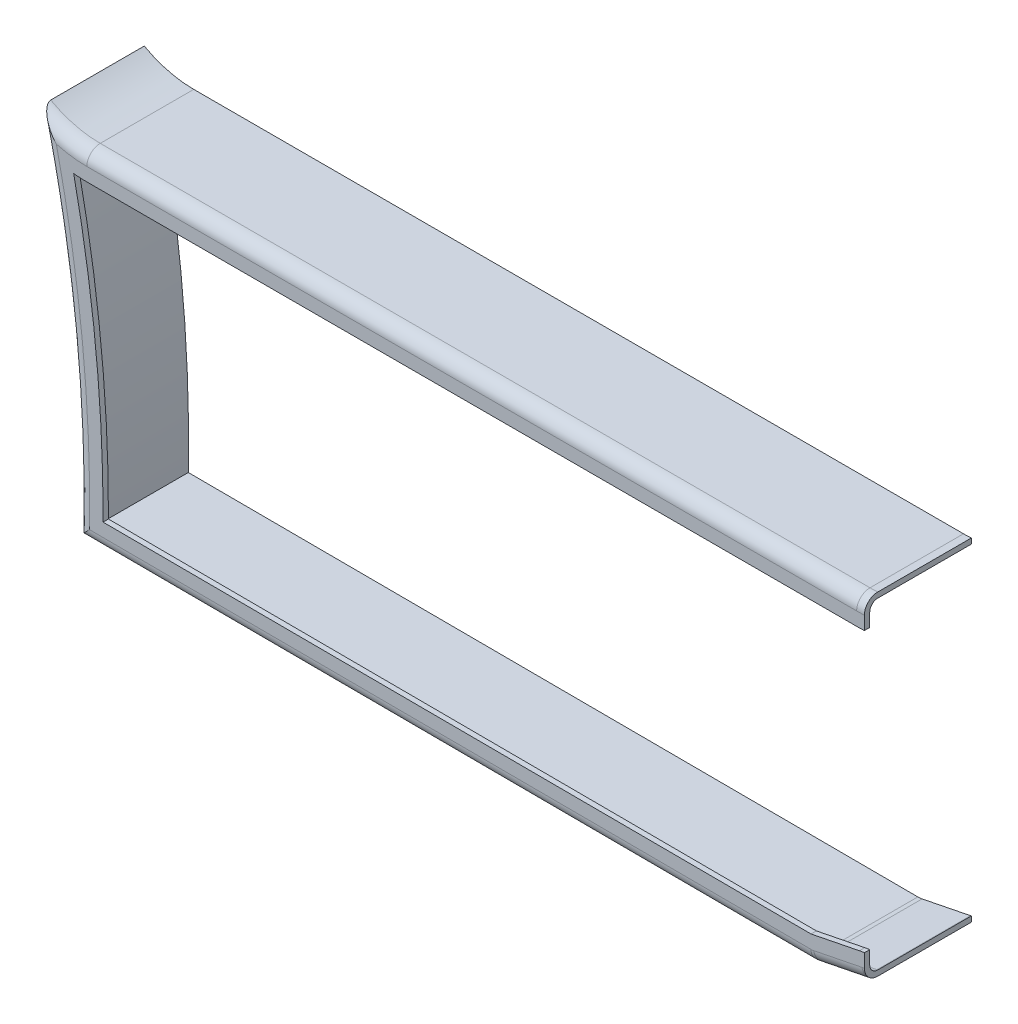
SolidWorks part; units mm, degrees
ref_plane "Front Plane" through (0, 0, 0) normal (0, 0, 1) x (1, 0, 0)
ref_plane "Top Plane" through (0, 0, 0) normal (0, 1, 0) x (1, 0, 0)
ref_plane "Right Plane" through (0, 0, 0) normal (1, 0, 0) x (0, 0, -1)
ref_plane "CAR IF PROFILE REFERENCE PLANE" through (0, 0, -4) normal (0, 0, 1) x (1, 0, 0)
sketch "CAR IF PROFILE (LINKED)" plane through (0, 0, -4) normal (0, 0, 1) x (1, 0, 0)
  line L0 (-295.0786, -111.9463) -> (-19, -113) construction
  line L1 (-19, -113) -> (1, -109) construction
  line L2 (403.25, -79.6442) -> (375, -16.4082) construction
  line L3 (-291, 15.25) -> (-2.9062, 15.25) construction
  line L4 (-295.0786, -111.9463) -> (-19, -113)
  line L5 (-19, -113) -> (1, -109)
  line L6 (403.25, -79.6442) -> (375, -16.4082)
  line L7 (-291, 15.25) -> (-2.9062, 15.25)
  arc A0 (-295.0786, -111.9463) -> (-309.5161, 20.0475) centre (-794.9319, -99.8337) ccw construction
  arc A1 (1, -109) -> (396.5667, -90.8831) centre (-84.789, 6091.6239) ccw construction
  arc A2 (396.5667, -90.8831) -> (403.25, -79.6442) centre (395.9457, -82.9073) ccw construction
  arc A3 (375, -16.4082) -> (355.6766, 0.25) centre (347.609, -28.6449) ccw construction
  arc A4 (355.6766, 0.25) -> (6.1335, 16.0739) centre (146.6563, -748.3762) ccw construction
  arc A5 (-2.9062, 15.25) -> (6.1335, 16.0739) centre (-2.9062, 65.25) ccw construction
  arc A6 (-309.5161, 20.0475) -> (-291, 15.25) centre (-291, 53.3805) ccw construction
  arc A7 (-295.0786, -111.9463) -> (-309.5161, 20.0475) centre (-794.9319, -99.8337) ccw
  arc A8 (1, -109) -> (396.5667, -90.8831) centre (-84.789, 6091.6239) ccw
  arc A9 (396.5667, -90.8831) -> (403.25, -79.6442) centre (395.9457, -82.9073) ccw
  arc A10 (375, -16.4082) -> (355.6766, 0.25) centre (347.609, -28.6449) ccw
  arc A11 (355.6766, 0.25) -> (6.1335, 16.0739) centre (146.6563, -748.3762) ccw
  arc A12 (-2.9062, 15.25) -> (6.1335, 16.0739) centre (-2.9062, 65.25) ccw
  arc A13 (-309.5161, 20.0475) -> (-291, 15.25) centre (-291, 53.3805) ccw
extrude "BULK EXTRUDE" add sketch "CAR IF PROFILE (LINKED)" along normal blind 15 and the other way blind 25
fillet "Fillet1" radius 10 2 edges at (-19, -113, -9) (1, -109, -9)
fillet "Fillet2" radius 5 13 edges at (-300.5637, 16.4689, 11) (-146.9531, 15.25, 11) (1.6324, 15.4564, 11) (181.8071, 28.087, 11) (367.1973, -5.9227, 11) (389.125, -48.0262, 11) (402.8219, -86.9962, 11) (199.3872, -103.0787, 11) (1.0041, -109.042, 11) (-8.9561, -110.9912, 11) (-19.0049, -112.9494, 11) (-297.8963, -45.468, 11) (-157.544, -112.4712, 11)
shell "Shell1" thickness 2 removed face at (47.0813, -50.7449, -29)
sketch "Sketch4" plane through (0, 0, 11) normal (0, 0, 1) x (1, 0, 0)
  line L8 (-2.9062, 5.25) -> (-291, 5.25)
  line L9 (-284.9364, -101.9849) -> (-19.9713, -102.9962)
  line L10 (-19.9713, -102.9962) -> (-1.8633, -99.3746)
  line L11 (392.9625, -81.1328) -> (365.8697, -20.4871)
  line L12 (-2.9062, 5.25) -> (-291, 5.25)
  line L13 (-284.9364, -101.9849) -> (-19.9713, -102.9962)
  line L14 (-19.9713, -102.9962) -> (-1.8633, -99.3746)
  line L15 (392.9625, -81.1328) -> (365.8697, -20.4871)
  arc A18 (-284.9364, -101.9849) -> (-295.9287, 5.503) centre (-794.9319, -99.8337) ccw
  arc A19 (1.7794, -98.9882) -> (-1.8633, -99.3746) centre (2.059, -118.9862) ccw
  arc A20 (1.7794, -98.9882) -> (392.9625, -81.1328) centre (-84.789, 6091.6239) ccw
  arc A21 (365.8697, -20.4871) -> (352.9874, -9.3816) centre (347.609, -28.6449) ccw
  arc A22 (352.9874, -9.3816) -> (7.9414, 6.2387) centre (146.6563, -748.3762) ccw
  arc A23 (-2.9062, 5.25) -> (7.9414, 6.2387) centre (-2.9062, 65.25) ccw
  arc A24 (-284.9364, -101.9849) -> (-295.9287, 5.503) centre (-794.9319, -99.8337) ccw
  arc A25 (1.7794, -98.9882) -> (-1.8633, -99.3746) centre (2.059, -118.9862) ccw
  arc A26 (1.7794, -98.9882) -> (392.9625, -81.1328) centre (-84.789, 6091.6239) ccw
  arc A27 (365.8697, -20.4871) -> (352.9874, -9.3816) centre (347.609, -28.6449) ccw
  arc A28 (352.9874, -9.3816) -> (7.9414, 6.2387) centre (146.6563, -748.3762) ccw
  arc A29 (-2.9062, 5.25) -> (7.9414, 6.2387) centre (-2.9062, 65.25) ccw
  arc A30 (-295.9287, 5.503) -> (-291, 5.25) centre (-291, 53.3805) ccw
  arc A31 (-295.9287, 5.503) -> (-291, 5.25) centre (-291, 53.3805) ccw
  dimension "D1" = 5
extrude "Cut-Extrude1" cut sketch "Sketch4" against normal through all
sketch "Sketch5" plane through (0, 0, 0) normal (1, 0, 0) x (0, 0, -1)
  line L1 (-227.9524, 132.4078) -> (252.9048, 132.4078)
  line L2 (-227.9524, 132.4078) -> (-227.9524, -220.2207)
  line L3 (-227.9524, -220.2207) -> (252.9048, -220.2207)
  line L4 (252.9048, 132.4078) -> (252.9048, -220.2207)
extrude "Cut-Extrude2" cut sketch "Sketch5" along normal through all
sketch "Sketch1" [suppressed] plane through (0, 0, 30) normal (0, 0, 1) x (1, 0, 0)
  line L0 (-291, 3.75) -> (-291, -100.25)
  line L1 (-285.5, -105.75) -> (30.5, -105.75)
  line L2 (35.5, -105.75) -> (351.5, -105.75)
  line L3 (357, -100.25) -> (357, 3.75)
  line L4 (33, -100.25) -> (33, 3.75)
  line L5 (30.5, 6.25) -> (-285.5, 6.25)
  line L6 (-288, 3.75) -> (-288, -100.25)
  line L7 (-285.5, -102.75) -> (30.5, -102.75)
  line L9 (30.5, 6.25) -> (-285.5, 6.25)
  line L10 (-288, 3.75) -> (-288, -100.25)
  line L11 (-285.5, -102.75) -> (30.5, -102.75)
  line L12 (354, -100.25) -> (354, 3.75)
  line L13 (351.5, 6.25) -> (35.5, 6.25)
  line L14 (33, 3.75) -> (33, -100.25)
  line L15 (35.5, -102.75) -> (351.5, -102.75)
  line L16 (354, -100.25) -> (354, 3.75)
  line L17 (351.5, 6.25) -> (35.5, 6.25)
  line L19 (35.5, -102.75) -> (351.5, -102.75)
  line L20 (351.5, 9.25) -> (35.5, 9.25)
  line L21 (30.5, 9.25) -> (-285.5, 9.25)
  line L22 (30.5, -105.75) -> (35.5, -105.75)
  line L23 (30.5, 9.25) -> (35.5, 9.25)
  arc A0 (-285.5, 9.25) -> (-291, 3.75) centre (-285.5, 3.75) ccw
  arc A1 (-291, -100.25) -> (-285.5, -105.75) centre (-285.5, -100.25) ccw
  arc A4 (30.5, -102.75) -> (33, -100.25) centre (30.5, -100.25) ccw
  arc A5 (33, 3.75) -> (30.5, 6.25) centre (30.5, 3.75) ccw
  arc A6 (-285.5, 6.25) -> (-288, 3.75) centre (-285.5, 3.75) ccw
  arc A7 (-288, -100.25) -> (-285.5, -102.75) centre (-285.5, -100.25) ccw
  arc A8 (30.5, -102.75) -> (33, -100.25) centre (30.5, -100.25) ccw
  arc A9 (33, 3.75) -> (30.5, 6.25) centre (30.5, 3.75) ccw
  arc A10 (-285.5, 6.25) -> (-288, 3.75) centre (-285.5, 3.75) ccw
  arc A11 (-288, -100.25) -> (-285.5, -102.75) centre (-285.5, -100.25) ccw
  arc A12 (351.5, -102.75) -> (354, -100.25) centre (351.5, -100.25) ccw
  arc A13 (354, 3.75) -> (351.5, 6.25) centre (351.5, 3.75) ccw
  arc A14 (35.5, 6.25) -> (33, 3.75) centre (35.5, 3.75) ccw
  arc A15 (33, -100.25) -> (35.5, -102.75) centre (35.5, -100.25) ccw
  arc A16 (351.5, -102.75) -> (354, -100.25) centre (351.5, -100.25) ccw
  arc A17 (354, 3.75) -> (351.5, 6.25) centre (351.5, 3.75) ccw
  arc A18 (35.5, 6.25) -> (33, 3.75) centre (35.5, 3.75) ccw
  arc A19 (33, -100.25) -> (35.5, -102.75) centre (35.5, -100.25) ccw
  arc A20 (351.5, -105.75) -> (357, -100.25) centre (351.5, -100.25) ccw
  arc A21 (357, 3.75) -> (351.5, 9.25) centre (351.5, 3.75) ccw
  arc A24 (33, 8.649) -> (30.5, 9.25) centre (30.5, 3.75) ccw construction
  arc A25 (35.5, 9.25) -> (33, 8.649) centre (35.5, 3.75) ccw construction
  arc A26 (30.5, -105.75) -> (33, -105.149) centre (30.5, -100.25) ccw construction
  arc A27 (33, -105.149) -> (35.5, -105.75) centre (35.5, -100.25) ccw construction
  dimension "D1" = 0
  dimension "D2" = 0
  dimension "D3" = 3
extrude "Boss-Extrude1" [suppressed] add sketch "Sketch1" against normal blind 2.25
sketch "Sketch2" [suppressed] plane through (0, 0, 27.75) normal (0, 0, -1) x (-1, 0, 0)
  line L0 (-36, 3.75) -> (-351, 3.75) construction
  line L1 (285, 3.75) -> (-30, 3.75) construction
  line L2 (285, -100.25) -> (285, 3.75) construction
  line L3 (162.5, -102.75) -> (162.5, -100.25) construction
  line L4 (285.5, 9.25) -> (-351.5, 9.25)
  line L5 (-357, 3.75) -> (-357, -100.25)
  line L6 (-351.5, -105.75) -> (285.5, -105.75)
  line L7 (291, -100.25) -> (291, 3.75)
  line L8 (285.5, 9.25) -> (-351.5, 9.25)
  line L9 (-357, 3.75) -> (-357, -100.25)
  line L10 (-351.5, -105.75) -> (285.5, -105.75)
  line L11 (291, -100.25) -> (291, 3.75)
  line L12 (162.5, -100.25) -> (285, -100.25) construction
  line L13 (92.5, -100.25) -> (92.5, -102.75) construction
  line L14 (-30, -100.25) -> (92.5, -100.25) construction
  line L15 (-30, 3.75) -> (-30, -100.25) construction
  line L16 (-36, -100.25) -> (-36, 3.75) construction
  line L17 (-158.5, -100.25) -> (-36, -100.25) construction
  line L18 (-158.5, -102.75) -> (-158.5, -100.25) construction
  line L19 (-228.5, -100.25) -> (-228.5, -102.75) construction
  line L20 (-351, -100.25) -> (-228.5, -100.25) construction
  line L21 (-351, 3.75) -> (-351, -100.25) construction
  line L22 (-36, 3.75) -> (-351, 3.75)
  line L23 (285, 3.75) -> (-30, 3.75)
  line L24 (285, -100.25) -> (285, 3.75)
  line L25 (162.5, -102.75) -> (162.5, -100.25)
  line L26 (162.5, -100.25) -> (285, -100.25)
  line L27 (92.5, -100.25) -> (92.5, -102.75)
  line L28 (-30, -100.25) -> (92.5, -100.25)
  line L29 (-30, 3.75) -> (-30, -100.25)
  line L30 (-36, -100.25) -> (-36, 3.75)
  line L31 (-158.5, -100.25) -> (-36, -100.25)
  line L32 (-158.5, -102.75) -> (-158.5, -100.25)
  line L33 (-228.5, -100.25) -> (-228.5, -102.75)
  line L34 (-351, -100.25) -> (-228.5, -100.25)
  line L35 (-351, 3.75) -> (-351, -100.25)
  arc A4 (291, 3.75) -> (285.5, 9.25) centre (285.5, 3.75) ccw
  arc A5 (-351.5, 9.25) -> (-357, 3.75) centre (-351.5, 3.75) ccw
  arc A6 (-357, -100.25) -> (-351.5, -105.75) centre (-351.5, -100.25) ccw
  arc A7 (285.5, -105.75) -> (291, -100.25) centre (285.5, -100.25) ccw
  arc A8 (291, 3.75) -> (285.5, 9.25) centre (285.5, 3.75) ccw
  arc A9 (-351.5, 9.25) -> (-357, 3.75) centre (-351.5, 3.75) ccw
  arc A10 (-357, -100.25) -> (-351.5, -105.75) centre (-351.5, -100.25) ccw
  arc A11 (285.5, -105.75) -> (291, -100.25) centre (285.5, -100.25) ccw
  line M9 (285.5, -102.75) -> (-30.5, -102.75)
  arc M10 (-30.5, -102.75) -> (-33, -100.25) centre (-30.5, -100.25) cw
  arc M11 (-33, -100.25) -> (-35.5, -102.75) centre (-35.5, -100.25) cw
  line M12 (-35.5, -102.75) -> (-351.5, -102.75)
  arc M13 (-351.5, -102.75) -> (-354, -100.25) centre (-351.5, -100.25) cw
  line M14 (-354, -100.25) -> (-354, 3.75)
  arc M15 (-354, 3.75) -> (-351.5, 6.25) centre (-351.5, 3.75) cw
  line M16 (-351.5, 6.25) -> (-35.5, 6.25)
  arc M17 (-35.5, 6.25) -> (-33, 3.75) centre (-35.5, 3.75) cw
  arc M18 (-33, 3.75) -> (-30.5, 6.25) centre (-30.5, 3.75) cw
  line M19 (-30.5, 6.25) -> (285.5, 6.25)
  arc M20 (285.5, 6.25) -> (288, 3.75) centre (285.5, 3.75) cw
  line M21 (288, 3.75) -> (288, -100.25)
  arc M22 (288, -100.25) -> (285.5, -102.75) centre (285.5, -100.25) cw
  arc M23 (291, 3.75) -> (285.5, 9.25) centre (285.5, 3.75) ccw
  line M24 (285.5, 9.25) -> (-351.5, 9.25)
  arc M25 (-351.5, 9.25) -> (-357, 3.75) centre (-351.5, 3.75) ccw
  line M26 (-357, 3.75) -> (-357, -100.25)
  arc M27 (-357, -100.25) -> (-351.5, -105.75) centre (-351.5, -100.25) ccw
  line M28 (-351.5, -105.75) -> (285.5, -105.75)
  arc M29 (285.5, -105.75) -> (291, -100.25) centre (285.5, -100.25) ccw
  line M30 (291, -100.25) -> (291, 3.75)
  dimension "D1" = 0
extrude "Boss-Extrude2" [suppressed] add sketch "Sketch2" along normal blind 2.5 contours L35 L22 L30 L31 L32 L27 L28 L29 L23 L24 L26 L25 L33 L34 M12 M11 M10 M9 M22 M21 M20 M19 M18 M17 M16 M15 M14 M13 | M30 M23 M24 M25 M26 M27 M28 M29 M22 M9 M10 M11 M12 M13 M14 M15 M16 M17 M18 M19 M20 M21
